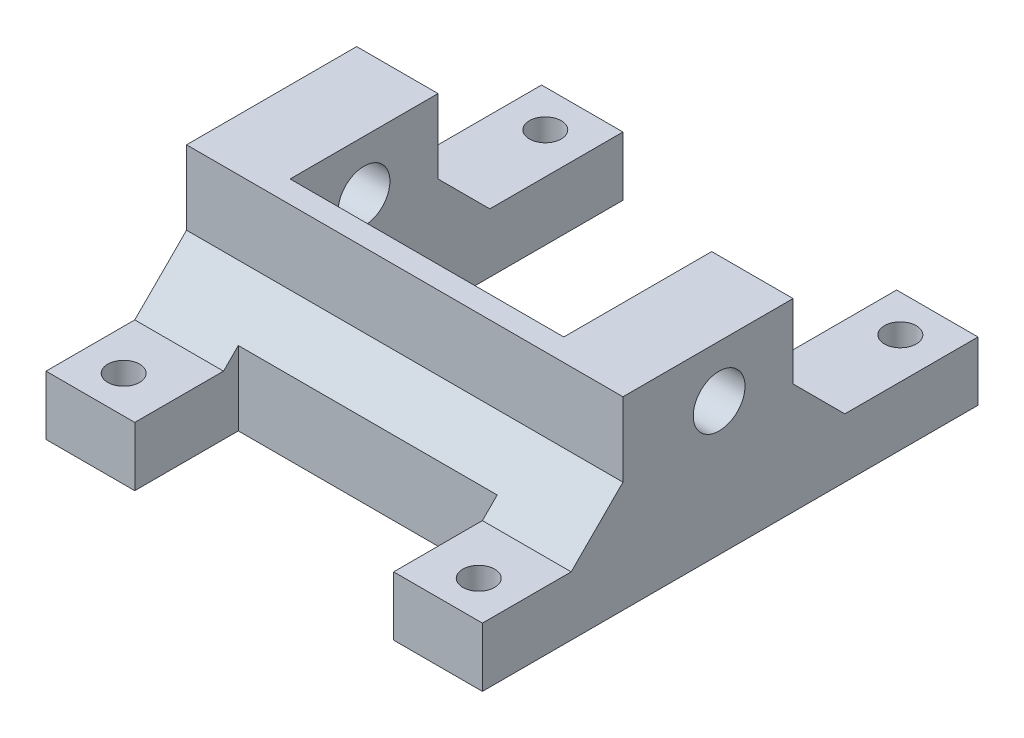
SolidWorks part; units mm, degrees
material "1060 合金"
ref_plane "前视基准面" through (0, 0, 0) normal (0, 0, 1) x (1, 0, 0)
ref_plane "上视基准面" through (0, 0, 0) normal (0, 1, 0) x (1, 0, 0)
ref_plane "右视基准面" through (0, 0, 0) normal (1, 0, 0) x (0, 0, -1)
sketch "草图1" plane through (0, 0, 0) normal (1, 0, 0) x (0, 0, -1)
  line L0 (0, 8) -> (0, 25)
  line L1 (0, 25) -> (23, 25)
  line L2 (23, 25) -> (23, 8)
  line L3 (23, 8) -> (48, 8)
  line L4 (48, 8) -> (48, 0)
  line L5 (48, 0) -> (-19, 0)
  line L6 (0, 8) -> (-19, 8)
  line L7 (-19, 8) -> (-19, 0)
  circle A0 centre (13, 18) radius 3.5
  dimension "D1" = 7
  dimension "D2" = 13
  dimension "D3" = 10
  dimension "D4" = 7
  dimension "D6" = 18
  dimension "D5" = 8
  dimension "D7" = 25
  dimension "D8" = 19
extrude "凸台-拉伸1" add sketch "草图1" along normal mid plane 59
sketch "草图3" plane through (0, 0, -23) normal (0, 0, -1) x (-1, 0, 0)
  line L0 (0, 0) -> (0, 31.1223) construction
  line L1 (-29.5, 25) -> (29.5, 25) construction
  line L2 (-18.5, 8) -> (18.5, 8)
  line L3 (-18.5, 8) -> (-18.5, 25)
  line L4 (-18.5, 25) -> (18.5, 25)
  line L5 (18.5, 8) -> (18.5, 25)
  line L6 (-18.5, 8) -> (18.5, 25) construction
  line L7 (-18.5, 25) -> (18.5, 8) construction
  line L8 (-29.5, 8) -> (29.5, 8) construction
  point P3 (0, 16.5)
  dimension "D1" = 37
extrude "切除-拉伸2" cut sketch "草图3" against normal offset from surface (20 mm away) 3 up to face at (0, 16.5, 0)
sketch "草图4" plane through (0, 8, 0) normal (0, 1, 0) x (1, 0, 0)
  line L0 (29.5, 48) -> (-29.5, 48) construction
  line L1 (-18.5, 3) -> (18.5, 3)
  line L2 (-18.5, 3) -> (-18.5, 48)
  line L3 (-18.5, 48) -> (18.5, 48)
  line L4 (18.5, 3) -> (18.5, 48)
  line L5 (-18.5, 3) -> (18.5, 48) construction
  line L6 (-18.5, 48) -> (18.5, 3) construction
  line L7 (29.5, -19) -> (-29.5, -19) construction
  line L8 (-17.5, -5) -> (17.5, -5)
  line L9 (-17.5, -5) -> (-17.5, -19)
  line L10 (-17.5, -19) -> (17.5, -19)
  line L11 (17.5, -5) -> (17.5, -19)
  line L12 (-17.5, -5) -> (17.5, -19) construction
  line L13 (-17.5, -19) -> (17.5, -5) construction
  line L14 (0, 25.5) -> (0, -12) construction
  line L15 (29.5, 0) -> (29.5, -19) construction
  line L16 (29.5, 0) -> (-29.5, 0) construction
  line L18 (-18.5, 3) -> (18.5, 3) construction
  point P0 (0, 25.5)
  point P7 (0, -12)
  dimension "D1" = 12
  dimension "D2" = 5
extrude "切除-拉伸3" cut sketch "草图4" against normal up to next
hole_wizard "M4 间隙孔1" positions "草图6" profile "草图5" hole size "M4" standard "GB" end condition up to next
sketch "草图6" plane through (0, 0, 0) normal (0, -1, 0) x (-1, 0, 0)
  line L0 (0, 0) -> (0, -27.3362) construction
  line L1 (24, 43) -> (24, -14) construction
  line L3 (-29.5, -19) -> (-17.5, -19) construction
  line L4 (18.5, 48) -> (29.5, 48) construction
  point P0 (24, -14)
  point P13 (24, 43)
  point P27 (-24, -14)
  point P28 (-24, 43)
  dimension "D1" = 48
  dimension "D2" = 5
  dimension "D3" = 5
sketch "草图5" plane through (-24, 0, 14) normal (1, 0, 0) x (0, 0, -1)
  line L0 (0, 0) -> (0, 8)
  line L1 (0, 8) -> (2.15, 8)
  line L2 (2.15, 8) -> (2.15, 0)
  line L5 (2.15, 0) -> (0, 0)
  line L11 (0, -6.35) -> (0, 107.95) construction
  dimension "通孔孔直径" = 4.3
  dimension "通孔孔深度" = 8
chamfer "倒角1" distance 7 angle 45 3 edges at (0, 8, 0) (24, 8, -23) (-24, 8, -23)
move or copy body "实体-移动/复制1" [suppressed] bodies to move or copy 111
